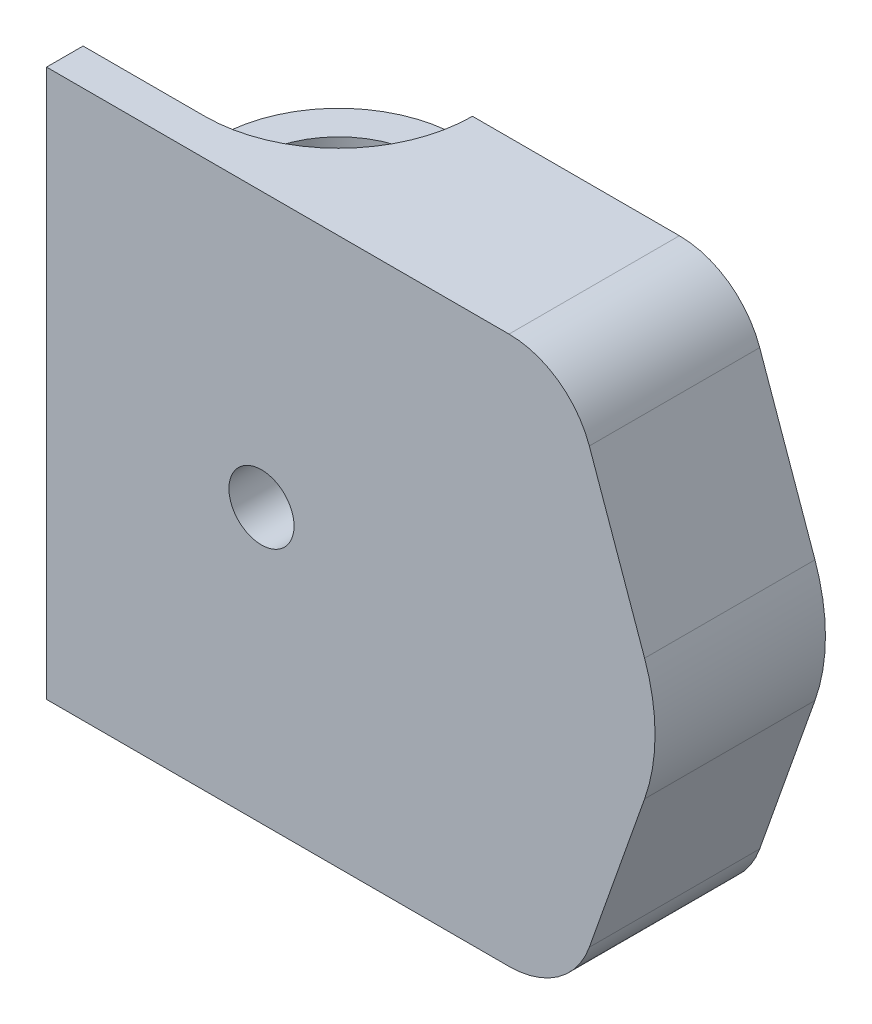
SolidWorks part; units mm, degrees
ref_plane "Front Plane" through (0, 0, 0) normal (0, 0, 1) x (1, 0, 0)
ref_plane "Top Plane" through (0, 0, 0) normal (0, 1, 0) x (1, 0, 0)
ref_plane "Right Plane" through (0, 0, 0) normal (1, 0, 0) x (0, 0, -1)
sketch "Sketch1" plane through (0, 0, 0) normal (0, 0, 1) x (1, 0, 0)
  line L0 (137.8275, 74.872) -> (187.8275, 74.872) construction
  line L1 (171.8275, 52.372) -> (171.8275, 97.372) construction
  line L2 (325.8275, 52.372) -> (325.8275, 97.372) construction
  line L6 (182.4263, 92.7077) -> (186.9678, 79.8771)
  line L7 (182.4263, 57.0363) -> (186.9678, 69.8669)
  line L473 (137.8275, 85.372) -> (157.8275, 85.372)
  line L475 (137.8275, 64.372) -> (157.8275, 64.372)
  line L476 (137.8275, 85.372) -> (137.8275, 64.372)
  line L480 (157.8275, 97.372) -> (157.8275, 85.372)
  line L481 (157.8275, 64.372) -> (157.8275, 52.372)
  line L505 (175.8275, 52.372) -> (157.8275, 52.372)
  line L506 (175.8275, 97.372) -> (157.8275, 97.372)
  arc A0 (182.4263, 92.7077) -> (175.8275, 97.372) centre (175.8275, 90.372) ccw
  arc A1 (175.8275, 52.372) -> (182.4263, 57.0363) centre (175.8275, 59.372) ccw
  arc A2 (186.9678, 69.8669) -> (186.9678, 79.8771) centre (172.8275, 74.872) ccw
  circle A35 centre (155.4875, 74.872) radius 2.675
  circle A36 centre (173.6339, 74.872) radius 6.75
  dimension "D1" = 5.35
  dimension "D8" = 7
  dimension "D9" = 7
  dimension "D6" = 13.5
  dimension "D7" = 17.66
  dimension "D11" = 15.5
  dimension "D5" = 14.1936
  dimension "D2" = 21
  dimension "D3" = 45
  dimension "D4" = 20
  dimension "D10" = 50
  dimension "D13" = 154
extrude "Boss-Extrude6" add sketch "Sketch1" along normal blind 10
sketch "Sketch9" plane through (0, 85.372, 0) normal (0, 1, 0) x (1, 0, 0)
  line L0 (137.8275, 0) -> (157.8275, 0) construction
  line L1 (137.8275, 0) -> (157.8275, 0)
  line L2 (147.8123, 10) -> (137.8275, 10)
  line L3 (137.8275, 10) -> (137.8275, 0)
  arc A0 (157.8275, 0) -> (147.8123, 10) centre (147.8275, 0) ccw
extrude "Boss-Extrude8" add sketch "Sketch9" against normal up to vertex
sketch "Sketch10" plane through (0, 85.372, 0) normal (0, 1, 0) x (1, 0, 0)
  circle A0 centre (147.8275, 0) radius 3.5
  dimension "D1" = 7
extrude "Cut-Extrude5" cut sketch "Sketch10" against normal through all
sketch "Sketch11" plane through (0, 85.372, 0) normal (0, 1, 0) x (1, 0, 0)
  circle A0 centre (147.8275, 0) radius 7.125
  dimension "D1" = 14.25
extrude "Cut-Extrude6" cut sketch "Sketch11" against normal blind 5
sketch "Sketch12" plane through (0, 64.372, 0) normal (0, -1, 0) x (1, 0, 0)
  circle A0 centre (147.8275, 0) radius 7.125 construction
  circle A1 centre (147.8275, 0) radius 7.125
extrude "Cut-Extrude7" cut sketch "Sketch12" against normal blind 5
sketch "Sketch14" plane through (0, 0, 10) normal (0, 0, 1) x (1, 0, 0)
  line L0 (137.8275, 85.372) -> (157.8275, 85.372) construction
  line L1 (157.8979, 79.047) -> (153.077, 79.047)
  line L2 (153.077, 79.047) -> (150.6666, 74.872)
  line L3 (150.6666, 74.872) -> (153.077, 70.697)
  line L4 (153.077, 70.697) -> (157.8979, 70.697)
  line L5 (157.8979, 70.697) -> (160.3083, 74.872)
  line L6 (160.3083, 74.872) -> (157.8979, 79.047)
  circle A0 centre (155.4875, 74.872) radius 4.175 construction
  dimension "D1" = 8.35
sketch "Sketch15" plane through (0, 0, 10) normal (0, 0, 1) x (1, 0, 0)
  line L0 (157.8979, 79.047) -> (153.077, 79.047) construction
  line L1 (153.077, 79.047) -> (150.6666, 74.872) construction
  line L2 (150.6666, 74.872) -> (153.077, 70.697) construction
  line L3 (153.077, 70.697) -> (157.8979, 70.697) construction
  line L4 (157.8979, 70.697) -> (160.3083, 74.872) construction
  line L5 (160.3083, 74.872) -> (157.8979, 79.047) construction
  line L6 (157.8979, 79.047) -> (153.077, 79.047)
  line L7 (153.077, 79.047) -> (150.6666, 74.872)
  line L8 (150.6666, 74.872) -> (153.077, 70.697)
  line L9 (153.077, 70.697) -> (157.8979, 70.697)
  line L10 (157.8979, 70.697) -> (160.3083, 74.872)
  line L11 (160.3083, 74.872) -> (157.8979, 79.047)
extrude "Boss-Extrude9" add sketch "Sketch15" against normal blind 5
sketch "Sketch18" plane through (0, 0, 0) normal (0, 0, -1) x (-1, 0, 0)
  circle A2 centre (-173.6339, 74.872) radius 6.75 construction
  circle A8 centre (-173.6339, 74.872) radius 6.75
sketch "Sketch19" plane through (0, 85.372, 0) normal (0, 1, 0) x (1, 0, 0)
  line L0 (157.8275, -4.5826) -> (157.8275, -10)
  line L1 (157.8275, -10) -> (152.41, -10)
  arc A2 (152.41, -10) -> (157.8275, -4.5826) centre (147.8275, 0) ccw
  dimension "D1" = 11
extrude "Boss-Extrude11" add sketch "Sketch19" along normal up to surface (12 mm away) up to face at (166.8275, 97.372, 5)
sketch "Sketch21" plane through (0, 64.372, 0) normal (0, -1, 0) x (1, 0, 0)
  line L0 (157.8275, 4.5826) -> (157.8275, 10) construction
  line L1 (157.8275, 10) -> (152.41, 10) construction
  line L3 (157.8275, 4.5826) -> (157.8275, 10)
  line L4 (157.8275, 10) -> (152.41, 10)
  arc A1 (157.8275, 4.5826) -> (152.41, 10) centre (147.8275, 0) ccw
  dimension "D1" = 11
extrude "Boss-Extrude13" add sketch "Sketch21" along normal up to surface (12 mm away) up to face at (166.8275, 52.372, 5)
extrude "Cut-Extrude11" cut sketch "Sketch18" against normal blind 1.67
sketch "Sketch23" plane through (0, 64.372, 0) normal (0, -1, 0) x (1, 0, 0)
  line L0 (157.8275, 4.5826) -> (157.8275, 0)
  line L1 (157.8275, 0) -> (158.8275, 0)
  arc A0 (158.8275, 0) -> (157.8275, 4.5826) centre (147.8275, 0) ccw
extrude "Cut-Extrude13" cut sketch "Sketch23" along normal through all
sketch "Sketch24" plane through (0, 85.372, 0) normal (0, 1, 0) x (1, 0, 0)
  line L0 (157.8275, -4.5826) -> (157.8275, 0)
  line L1 (157.8275, 0) -> (158.8275, 0)
  arc A0 (157.8275, -4.5826) -> (158.8275, 0) centre (147.8275, 0) ccw
extrude "Cut-Extrude14" cut sketch "Sketch24" along normal through all
extrude "Cut-Extrude10" cut sketch "Sketch14" against normal through all
sketch "Sketch26" plane through (0, 0, 10) normal (0, 0, 1) x (1, 0, 0)
  line L6 (153.077, 79.047) -> (150.6666, 74.872)
  line L7 (150.6666, 74.872) -> (153.077, 70.697)
  line L8 (153.077, 70.697) -> (157.8979, 70.697)
  line L9 (157.8979, 70.697) -> (160.3083, 74.872)
  line L10 (160.3083, 74.872) -> (157.8979, 79.047)
  line L11 (157.8979, 79.047) -> (153.077, 79.047)
  circle A0 centre (155.4875, 74.872) radius 4.175 construction
  circle A1 centre (155.4875, 74.872) radius 2.675
  dimension "D1" = 5.35
  dimension "D2" = 8.35
extrude "Boss-Extrude14" add sketch "Sketch26" against normal blind 5
sketch "Sketch27" plane through (0, 0, 10) normal (0, 0, 1) x (1, 0, 0)
  line L2 (137.8275, 85.372) -> (137.8275, 64.372) construction
  line L11 (137.8275, 85.372) -> (137.8275, 64.372)
  line L17 (172.8275, 74.872) -> (341.431, 74.872)
  circle A3 centre (155.4875, 74.872) radius 2.675 construction
  circle A7 centre (155.4875, 74.872) radius 2.675
  dimension "D1" = 5.35
extrude "Boss-Extrude15" add sketch "Sketch27" against normal blind 5
sketch "Sketch30" plane through (0, 0, 5) normal (0, 0, -1) x (-1, 0, 0)
  line L0 (-151.8718, 76.9595) -> (-159.1031, 72.7845) construction
  line L1 (-153.077, 79.047) -> (-150.6666, 74.872) construction
  line L2 (-157.8979, 70.697) -> (-160.3083, 74.872) construction
  circle A0 centre (-155.4875, 74.872) radius 2.675
  dimension "D1" = 5.35
extrude "Cut-Extrude15" cut sketch "Sketch30" against normal blind 10
sketch "Sketch31" plane through (0, 0, 1.67) normal (0, 0, -1) x (-1, 0, 0)
  line L13 (-157.8275, 85.372) -> (-158.8275, 85.372)
  line L14 (-157.8275, 64.372) -> (-157.8275, 70.697)
  line L15 (-157.8275, 70.697) -> (-157.8979, 70.697)
  line L16 (-157.8979, 70.697) -> (-160.3083, 74.872)
  line L17 (-160.3083, 74.872) -> (-157.8979, 79.047)
  line L18 (-157.8979, 79.047) -> (-157.8275, 79.047)
  line L19 (-157.8275, 79.047) -> (-157.8275, 85.372)
  line L20 (-157.8275, 85.372) -> (-158.8275, 85.372)
  line L22 (-158.8275, 97.372) -> (-175.8275, 97.372)
  line L23 (-182.4263, 92.7077) -> (-186.9678, 79.8771)
  line L24 (-186.9678, 69.8669) -> (-182.4263, 57.0363)
  line L25 (-175.8275, 52.372) -> (-158.8275, 52.372)
  line L26 (-158.8275, 52.372) -> (-158.8275, 64.372)
  line L27 (-158.8275, 64.372) -> (-157.8275, 64.372)
  line L28 (-157.8275, 64.372) -> (-157.8275, 70.697)
  line L29 (-157.8275, 70.697) -> (-157.8979, 70.697)
  line L30 (-157.8979, 70.697) -> (-160.3083, 74.872)
  line L31 (-160.3083, 74.872) -> (-157.8979, 79.047)
  line L32 (-157.8979, 79.047) -> (-157.8275, 79.047)
  line L33 (-157.8275, 79.047) -> (-157.8275, 85.372)
  line L34 (-158.8275, 85.372) -> (-158.8275, 97.372)
  line L35 (-158.8275, 85.372) -> (-158.8275, 97.372)
  line L36 (-158.8275, 97.372) -> (-175.8275, 97.372)
  line L37 (-182.4263, 92.7077) -> (-186.9678, 79.8771)
  line L38 (-186.9678, 69.8669) -> (-182.4263, 57.0363)
  line L39 (-175.8275, 52.372) -> (-158.8275, 52.372)
  line L40 (-158.8275, 52.372) -> (-158.8275, 64.372)
  line L41 (-158.8275, 64.372) -> (-157.8275, 64.372)
  circle A0 centre (-173.6339, 74.872) radius 6.75
  arc A4 (-175.8275, 97.372) -> (-182.4263, 92.7077) centre (-175.8275, 90.372) ccw
  arc A5 (-186.9678, 79.8771) -> (-186.9678, 69.8669) centre (-172.8275, 74.872) ccw
  arc A6 (-182.4263, 57.0363) -> (-175.8275, 52.372) centre (-175.8275, 59.372) ccw
  arc A7 (-175.8275, 97.372) -> (-182.4263, 92.7077) centre (-175.8275, 90.372) ccw
  arc A8 (-186.9678, 79.8771) -> (-186.9678, 69.8669) centre (-172.8275, 74.872) ccw
  arc A9 (-182.4263, 57.0363) -> (-175.8275, 52.372) centre (-175.8275, 59.372) ccw
  dimension "D1" = 0
extrude "Boss-Extrude16" add sketch "Sketch31" along normal up to surface (1.67 mm away) up to face at (166.8839, 74.872, 0)
sketch "Sketch32" plane through (0, 0, 0) normal (0, 0, -1) x (-1, 0, 0)
  circle A0 centre (-173.6339, 74.872) radius 6.75
extrude "Boss-Extrude17" add sketch "Sketch32" against normal blind 2
sketch "Sketch34" plane through (0, 0, 0) normal (0, 0, -1) x (-1, 0, 0)
  circle A5 centre (-173.6339, 74.872) radius 6.35
extrude "Boss-Extrude18" add sketch "Sketch34" along normal blind 1.5
sketch "Sketch35" plane through (0, 0, 10) normal (0, 0, 1) x (1, 0, 0)
  line L2 (137.8275, 85.372) -> (137.8275, 64.372) construction
  line L5 (175.8275, 52.372) -> (157.8275, 52.372) construction
  line L6 (182.4263, 57.0363) -> (186.9678, 69.8669) construction
  line L7 (182.4263, 92.7077) -> (186.9678, 79.8771) construction
  line L8 (175.8275, 97.372) -> (157.8275, 97.372) construction
  line L11 (137.8275, 85.372) -> (137.8275, 64.372)
  line L14 (175.8275, 52.372) -> (137.8275, 52.372)
  line L15 (182.4263, 57.0363) -> (186.9678, 69.8669)
  line L16 (182.4263, 92.7077) -> (186.9678, 79.8771)
  line L17 (175.8275, 97.372) -> (137.8275, 97.372)
  line L18 (137.8275, 85.372) -> (137.8275, 97.372)
  line L20 (137.8275, 64.372) -> (137.8275, 52.372)
  arc A0 (175.8275, 52.372) -> (182.4263, 57.0363) centre (175.8275, 59.372) ccw construction
  arc A1 (186.9678, 69.8669) -> (186.9678, 79.8771) centre (172.8275, 74.872) ccw construction
  arc A2 (182.4263, 92.7077) -> (175.8275, 97.372) centre (175.8275, 90.372) ccw construction
  circle A4 centre (155.4875, 74.872) radius 2.675 construction
  arc A5 (175.8275, 52.372) -> (182.4263, 57.0363) centre (175.8275, 59.372) ccw
  arc A6 (186.9678, 69.8669) -> (186.9678, 79.8771) centre (172.8275, 74.872) ccw
  arc A7 (182.4263, 92.7077) -> (175.8275, 97.372) centre (175.8275, 90.372) ccw
  circle A9 centre (155.4875, 74.872) radius 2.675
extrude "Boss-Extrude19" add sketch "Sketch35" along normal blind 4
sketch "Sketch36" plane through (0, 97.372, 0) normal (0, 1, 0) x (1, 0, 0)
  line L0 (147.8275, -11) -> (137.8275, -11)
  line L1 (137.8275, -14) -> (137.8275, -10) construction
  line L2 (137.8275, -11) -> (137.8275, -10)
  line L4 (137.8275, -10) -> (152.41, -10)
  arc A0 (147.8275, -11) -> (152.41, -10) centre (147.8275, 0) ccw
extrude "Cut-Extrude16" cut sketch "Sketch36" against normal up to surface (12 mm away) up to face at (148.1301, 85.372, 1.4774)
sketch "Sketch38" plane through (0, 52.372, 0) normal (0, -1, 0) x (1, 0, 0)
  line L0 (147.8275, 11) -> (137.8275, 11) construction
  line L1 (137.8275, 11) -> (137.8275, 10) construction
  line L2 (137.8275, 10) -> (152.41, 10) construction
  line L3 (147.8275, 11) -> (137.8275, 11)
  line L4 (137.8275, 11) -> (137.8275, 10)
  line L5 (137.8275, 10) -> (152.41, 10)
  arc A0 (152.41, 10) -> (147.8275, 11) centre (147.8275, 0) ccw construction
  arc A1 (152.41, 10) -> (147.8275, 11) centre (147.8275, 0) ccw
extrude "Cut-Extrude17" cut sketch "Sketch38" against normal up to surface (12 mm away) up to face at (148.1301, 64.372, 1.4774)
fillet "Fillet1" radius 10 1 edges at (137.8275, 74.872, -10)
